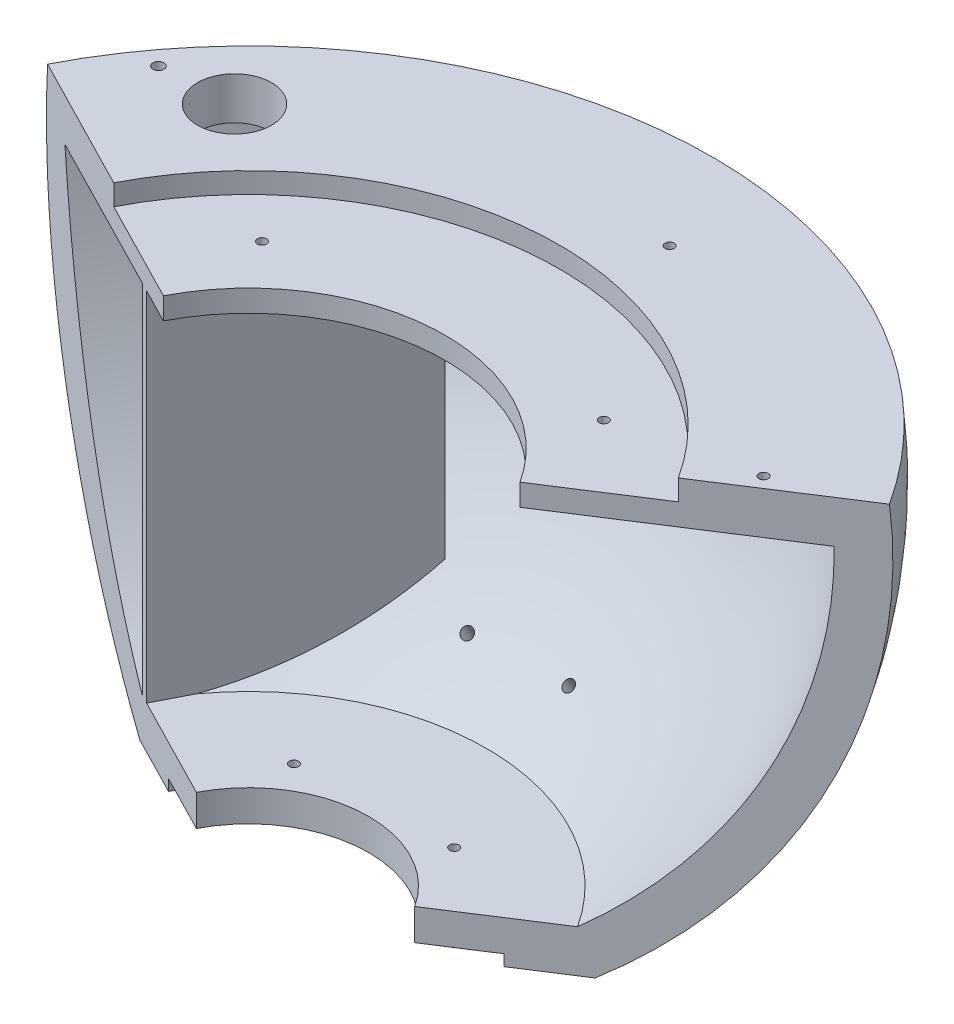
SolidWorks part; units mm, degrees
ref_plane "Plan de face" through (0, 0, 0) normal (0, 0, 1) x (1, 0, 0)
ref_plane "Plan de dessus" through (0, 0, 0) normal (0, 1, 0) x (1, 0, 0)
ref_plane "Plan de droite" through (0, 0, 0) normal (1, 0, 0) x (0, 0, -1)
sketch "Esquisse1" plane through (0, 0, 0) normal (0, 0, 1) x (1, 0, 0)
  line L0 (62.652, -45.2683) -> (117.5387, 212.9533) construction
  line L1 (0.3341, -92.6254) -> (0.3341, 171)
  line L2 (0, -110) -> (0, -296.0954) construction
  line L3 (0.3341, -92.6254) -> (59.3341, -92.6254)
  line L4 (0.3341, -92.6254) -> (0.3341, -77.5539) construction
  line L5 (0, 130.8616) -> (102, 130.8616) construction
  arc A0 (59.3341, -92.6254) -> (109.3586, 11.8616) centre (0, 0) ccw
  arc A1 (102, 130.8616) -> (83, 190.149) centre (0, 130.8616) ccw
  arc A3 (83, 190.149) -> (0.3341, 171) centre (15.1332, 295.1209) cw
  spline S0 degree 3 poles (102, 130.8616) (103.479, 113.6847) (71.2053, 65.5607) (110.7074, 34.2525) (109.3586, 11.8616) knots 0 0 0 0 0.406613 1 1 1 1
  dimension "D1" = 220
  dimension "D2" = 130.8616
  dimension "D3" = 102
  dimension "D8" = 12
  dimension "D9" = 110
  dimension "D12" = 59
  dimension "D13" = 281.0002
  dimension "D14" = 125
  dimension "D15" = 110
  dimension "D4" = 119
  dimension "D5" = 90
  dimension "D6" = 106
  dimension "D7" = 54
  dimension "D10" = 281
  dimension "D11" = 83
  dimension "D16" = 102
  dimension "D17" = 104.4869
revolve "Révolution2" add sketch "Esquisse1" angle 360 about L1
sketch "Esquisse2" plane through (0, 0, 0) normal (0, 1, 0) x (1, 0, 0)
  line L0 (0.3341, 0) -> (-105.6003, 54.3362) construction
  line L1 (0.3341, 0) -> (98.5184, 63.3863) construction
  line L2 (0.3341, 0) -> (6.0228, -114.443) construction
  dimension "D1" = 120
  dimension "D2" = 120
sketch "Esquisse3" plane through (0, 0, 0) normal (0, 1, 0) x (1, 0, 0)
  line L0 (0.3341, 0) -> (-105.6003, 54.3362) construction
  line L1 (0.3341, 0) -> (98.5184, 63.3863) construction
  line L2 (-97.2444, 50.0502) -> (0.3341, 0)
  line L3 (0.3341, 0) -> (92.4682, 59.4804)
  arc A0 (-97.2444, 50.0502) -> (92.4682, 59.4804) centre (0.3341, 0) ccw
  circle A1 centre (0.3341, 0) radius 109.6659 construction
extrude "Enlèv. mat.-Extru.1" cut sketch "Esquisse3" against normal mid plane 410
sketch "Esquisse4" plane through (0, 0, 0) normal (0, 0, 1) x (1, 0, 0)
  line L1 (107.6727, 198.3746) -> (-112, 198.3746)
  line L2 (107.6727, 198.3746) -> (107.6727, 11.3746)
  line L3 (107.6727, 11.3746) -> (-112, 11.3746)
  line L4 (-112, 198.3746) -> (-112, 11.3746)
  line L5 (-52.1629, -92.6254) -> (49.9021, -92.6254) construction
  dimension "D1" = 104
  dimension "D2" = 187
  dimension "D3" = 112
extrude "Enlèv. mat.-Extru.2" cut sketch "Esquisse4" against normal through all
shell "Coque2" thickness 10 removed face at (38.7311, -42.3994, -24.7885) removed face at (-40.3318, -42.3994, -20.8585)
ref_plane "Plan1" through (0, 11.5, 0) normal (0, 1, 0) x (1, 0, 0)
sketch "Esquisse6" plane through (0, 11.5, 0) normal (0, 1, 0) x (1, 0, 0)
  line L0 (0.3341, 0) -> (-105.6003, 54.3362) construction
  line L1 (0.3341, 0) -> (98.5184, 63.3863) construction
  line L2 (-64.7515, 33.3839) -> (0.3341, 0)
  line L3 (0.3341, 0) -> (61.7882, 39.6739)
  arc A0 (-64.7515, 33.3839) -> (61.7882, 39.6739) centre (0.3341, 0) cw
  dimension "D1" = 73.1479
extrude "Enlèv. mat.-Extru.4" cut sketch "Esquisse6" against normal blind 5
sketch "Esquisse7" plane through (0, 11.5, 0) normal (0, 1, 0) x (1, 0, 0)
  line L0 (0.3341, 0) -> (-105.6003, 54.3362) construction
  line L1 (0.3341, 0) -> (98.5184, 63.3863) construction
  line L2 (-40.7749, 21.0857) -> (0.3341, 0)
  line L3 (0.3341, 0) -> (39.1494, 25.0586)
  arc A0 (-40.7749, 21.0857) -> (39.1494, 25.0586) centre (0.3341, 0) cw
  dimension "D1" = 46.2013
extrude "Enlèv. mat.-Extru.5" cut sketch "Esquisse7" against normal blind 25
ref_plane "Plan2" through (0, -92.5, 0) normal (0, 1, 0) x (1, 0, 0)
sketch "Esquisse8" plane through (0, -92.5, 0) normal (0, 1, 0) x (1, 0, 0)
  line L0 (0.3341, 0) -> (98.5184, 63.3863) construction
  line L1 (0.3341, 0) -> (-105.6003, 54.3362) construction
  line L2 (36.8282, 23.56) -> (0.3341, 0)
  line L3 (0.3341, 0) -> (-38.3164, 19.8247)
  arc A0 (36.8282, 23.56) -> (-38.3164, 19.8247) centre (0.3341, 0) ccw
  dimension "D1" = 43.4383
extrude "Enlèv. mat.-Extru.6" cut sketch "Esquisse8" along normal mid plane 5
sketch "Esquisse10" plane through (0, -92.5, 0) normal (0, 1, 0) x (1, 0, 0)
  line L0 (0.3341, 0) -> (98.5184, 63.3863) construction
  line L1 (0.3341, 0) -> (-105.6003, 54.3362) construction
  line L2 (-24.8381, 12.9114) -> (0.3341, 0)
  line L3 (0.3341, 0) -> (24.1019, 15.3441)
  arc A0 (24.1019, 15.3441) -> (-24.8381, 12.9114) centre (0.3341, 0) ccw
  dimension "D1" = 28.2904
extrude "Enlèv. mat.-Extru.10" cut sketch "Esquisse10" along normal blind 15
scale "Echelle1" scale about centroid uniform scaling yes scale factor 1.15
sketch "Esquisse11" plane through (0, 17.974, 0) normal (0, 1, 0) x (1, 0, 0)
  arc A0 (106.2495, 57.3541) -> (-110.7469, 46.5678) centre (0.8651, -10.6805) ccw construction
  point P1 (-104.7658, 56.971)
  point P2 (-52.0649, 103.0429)
  dimension "D1" = 12
  dimension "D2" = 70
sketch3d "Esquisse3D1"
  line L1 (-52.0649, 17.974, -103.0429) -> (-104.7658, 17.974, -56.971)
  line L2 (-52.0649, 17.974, -103.0429) -> (-52.0649, 79.5177, -103.0429)
  line L3 (-52.0649, 79.5177, -103.0429) -> (-104.7658, 79.5177, -56.971)
  line L4 (-104.7658, 17.974, -56.971) -> (-104.7658, 79.5177, -56.971)
ref_plane "Plan4" through (-73.6133, 0, -84.2049) normal (-0.6582, 0, -0.7529) x (-0.7529, 0, 0.6582)
ref_plane "Plan5" through (-78.8787, 0, -90.2279) normal (-0.6582, 0, -0.7529) x (-0.7529, 0, 0.6582)
sketch "Esquisse21" plane through (-4.157, 0, 8.1046) normal (-0.4564, 0, 0.8898) x (0.8898, 0, 0.4564)
  line L0 (-58.7509, -90.126) -> (-26.8898, -90.126) construction
  line L1 (-57.9607, -90.126) -> (-108.9607, -90.126)
  line L2 (-57.9607, -90.126) -> (-57.9607, 6.474)
  line L3 (-57.9607, 6.474) -> (-108.9607, 6.474)
  line L4 (-108.9607, -90.126) -> (-108.9607, 6.474)
  line L5 (-47.4873, 6.474) -> (-108.9607, 6.474) construction
  arc A0 (-108.9607, 6.474) -> (-58.7509, -90.126) centre (6.0284, 4.8932) ccw construction
  dimension "D1" = 51
  dimension "D2" = 96.6
extrude "Boss.-Extru.2" add sketch "Esquisse21" against normal blind 60
sketch "Esquisse22" plane through (-4.157, 0, 8.1046) normal (-0.4564, 0, 0.8898) x (0.8898, 0, 0.4564)
  line L0 (-78.4759, 17.974) -> (-119.7934, 17.974) construction
  line L1 (-62.2058, -101.626) -> (-148.1886, -101.626)
  line L2 (6.0284, 27.594) -> (6.0284, -115.4103) construction
  line L3 (-119.7934, 17.974) -> (-148.1886, 17.974)
  line L4 (-148.1886, -101.626) -> (-148.1886, 17.974)
  arc A0 (-62.2058, -101.626) -> (-108.9607, -47.8302) centre (6.0284, 4.8932) cw
  arc A2 (-77.4797, -90.126) -> (-62.2058, -101.626) centre (6.0284, 4.8932) ccw construction
  arc A3 (-119.7934, 17.974) -> (-108.9607, -47.8302) centre (6.0284, 4.8932) ccw
  arc A4 (-119.7934, 17.974) -> (-108.9607, -47.8302) centre (6.0284, 4.8932) ccw construction
  point P6 (-108.9607, -47.8302)
revolve "Enlèvement de matière-Révolution1" cut sketch "Esquisse22" angle 360 about L2
sketch "Esquisse12" plane through (-78.8787, 0, -90.2279) normal (-0.6582, 0, -0.7529) x (-0.7529, 0, 0.6582)
  line L1 (-3.296, 1.2051) -> (9.704, 1.2051)
  line L2 (-3.296, 1.2051) -> (-3.296, -17.4949)
  line L3 (-3.296, -17.4949) -> (9.704, -17.4949)
  line L4 (9.704, 1.2051) -> (9.704, -17.4949)
  dimension "D1" = 13
  dimension "D2" = 18.7
  dimension "D3" = 3.296
  dimension "D4" = 1.2051
extrude "Enlèv. mat.-Extru.12" cut sketch "Esquisse12" against normal blind 50
sketch "Esquisse13" plane through (-78.8787, 0, -90.2279) normal (-0.6582, 0, -0.7529) x (-0.7529, 0, 0.6582)
  circle A0 centre (2.99, -80.5) radius 2.75
  dimension "D1" = 5.5
  dimension "D2" = 80.5
extrude "Enlèv. mat.-Extru.13" cut sketch "Esquisse13" against normal blind 50
sketch "Esquisse14" plane through (-78.8787, 0, -90.2279) normal (-0.6582, 0, -0.7529) x (-0.7529, 0, 0.6582)
  circle A0 centre (2.99, -80.5) radius 3.25
  dimension "D1" = 6.5
extrude "Enlèv. mat.-Extru.14" cut sketch "Esquisse14" against normal blind 42
sketch "Esquisse15" plane through (-78.8787, 0, -90.2279) normal (-0.6582, 0, -0.7529) x (-0.7529, 0, 0.6582)
  line L1 (-4.2483, 2.2976) -> (10.7517, 2.2976)
  line L2 (-4.2483, 2.2976) -> (-4.2483, -18.7024)
  line L3 (-4.2483, -18.7024) -> (10.7517, -18.7024)
  line L4 (10.7517, 2.2976) -> (10.7517, -18.7024)
  dimension "D1" = 15
  dimension "D2" = 21
  dimension "D3" = 2.2976
  dimension "D4" = 4.2483
extrude "Enlèv. mat.-Extru.15" cut sketch "Esquisse15" against normal blind 6.5
ref_plane "Plan7" through (0.4069, 0, -0.7932) normal (-0.4564, 0, 0.8898) x (0.8898, 0, 0.4564)
ref_plane "Plan8" through (-35.4394, 0, -40.5385) normal (-0.6582, 0, -0.7529) x (-0.7529, 0, 0.6582)
sketch "Esquisse23" plane through (-4.157, 0, 8.1046) normal (-0.4564, 0, 0.8898) x (0.8898, 0, 0.4564)
  line L0 (-60.5449, -74.5019) -> (-60.5449, -90.1574)
  line L1 (-108.9607, 6.474) -> (-60.5449, 6.474)
  line L4 (-60.5449, 6.474) -> (-60.5449, -74.5019)
  line L5 (-60.5449, -90.1574) -> (-60.6003, -90.1574)
  spline S0 degree 3 poles (-108.9607, 6.474) (-103.0847, -29.155) (-88.7059, -66.4238) (-60.6003, -90.1574) knots 0 0 0 0 1 1 1 1
extrude "Enlèv. mat.-Extru.16" cut sketch "Esquisse23" against normal blind 50
sketch "Esquisse24" plane through (0, 17.974, 0) normal (0, 1, 0) x (1, 0, 0)
  line L0 (-73.9834, 27.7109) -> (-110.7469, 46.5678) construction
  line L1 (106.2495, 57.3541) -> (71.5372, 34.9444) construction
  circle A0 centre (-76.1349, 62.5307) radius 10
  arc A1 (106.2495, 57.3541) -> (-110.7469, 46.5678) centre (0.8651, -10.6805) ccw construction
  circle A3 centre (0.5514, -4.3702) radius 101.767 construction
  point P10 (-92.3651, 37.1394)
  point P11 (88.8934, 46.1493)
  dimension "D1" = 20
  dimension "D2" = 30
  dimension "D3" = 77
  dimension "D4" = 62.5307
  dimension "D5" = 76.1349
extrude "Enlèv. mat.-Extru.17" cut sketch "Esquisse24" against normal blind 20
sketch "Esquisse25" plane through (0, -98.6068, 0) normal (0, -1, 0) x (1, 0, 0)
  line L0 (-1.615, -39.212) -> (0.3341, 0) construction
  line L1 (0.3341, 0) -> (6.0228, 114.443) construction
  line L2 (0.8656, 10.692) -> (19.7396, -26.1048) construction
  line L3 (-40.1239, -31.6247) -> (-47.9228, -31.6247) construction
  line L4 (0.8656, 10.692) -> (-21.5644, -24.0517) construction
  circle A0 centre (19.7396, -26.1048) radius 1.25
  circle A2 centre (-21.5644, -24.0517) radius 1.25
  circle A4 centre (-1.1875, -30.612) radius 1.25
  circle A5 centre (0.8656, 10.692) radius 41.355 construction
  arc A6 (-43.5831, -12.118) -> (42.8332, -16.4135) centre (0.8651, 10.6805) ccw construction
  point P1 (-1.615, -39.212)
  dimension "D1" = 8.6
  dimension "D5" = 2.5
  dimension "D3" = 2.5
  dimension "D6" = 30
  dimension "D2" = 82.71
  dimension "D4" = 30
hole_wizard "Trou taraudé M31" positions "Esquisse27" profile "Esquisse26" tap size "M3" standard "Iso"
sketch "Esquisse27" plane through (0, -98.6068, 0) normal (0, -1, 0) x (-1, 0, 0)
  point P0 (21.5644, 24.0517)
  point P5 (-19.7396, 26.1048)
sketch "Esquisse26" plane through (-21.5644, -98.6068, -24.0517) normal (1, 0, 0) x (0, 0, -1)
  line L0 (0, 0) -> (0, 13.2511)
  line L1 (0, 13.2511) -> (1.25, 12.5)
  line L2 (1.25, 12.5) -> (1.25, 0)
  line L5 (1.25, 0) -> (0, 0)
  line L10 (0, 13.2511) -> (-1.25, 12.5) construction
  line L11 (0, -6.35) -> (0, 107.95) construction
  dimension "Diamètre du trou pour taraudage" = 2.5
  dimension "Profondeur du trou pour taraudage" = 12.5
  dimension "Angle de pointe" = 118
cosmetic thread "Filetage de perçage1" parameters "D1"=8.4808, "D2"=3
cosmetic thread "Filetage de perçage3" parameters "D1"=8.4808, "D2"=3
sketch "Esquisse28" plane through (0, 12.3682, 0) normal (0, 1, 0) x (1, 0, 0)
  line L0 (-1.7727, 42.3855) -> (-3.3112, 73.3359) construction
  line L1 (-73.9834, 27.7109) -> (-46.4103, 13.5681) construction
  line L2 (45.5026, 18.1369) -> (71.5372, 34.9444) construction
  line L3 (-45.8023, 39.6351) -> (0.8651, -10.6805) construction
  line L4 (42.3125, 44.0151) -> (0.8651, -10.6805) construction
  circle A0 centre (0.8651, -10.6805) radius 68.6258 construction
  arc A1 (45.5026, 18.1369) -> (-46.4103, 13.5681) centre (0.8651, -10.6805) ccw construction
  circle A3 centre (-45.8023, 39.6351) radius 1.5
  circle A4 centre (-2.542, 57.8607) radius 1.5
  circle A5 centre (42.3125, 44.0151) radius 1.5
  arc A6 (71.5372, 34.9444) -> (-73.9834, 27.7109) centre (0.8651, -10.6805) ccw construction
  point P11 (-2.542, 57.8607)
  point P12 (-60.1968, 20.6395)
  point P13 (58.5199, 26.5406)
  dimension "D1" = 3
  dimension "D2" = 40
  dimension "D3" = 40
hole_wizard "Trou taraudé M32" positions "Esquisse3D2" profile "Esquisse29" tap size "M3" standard "Iso"
sketch3d "Esquisse3D2"
  point P0 (-45.8023, 12.3682, -39.6351)
  point P6 (42.3125, 12.3682, -44.0151)
sketch "Esquisse29" plane through (-45.8023, 12.3682, -39.6351) normal (1, 0, 0) x (0, 0, 1)
  line L0 (0, 0) -> (0, 13.2511)
  line L1 (0, 13.2511) -> (1.25, 12.5)
  line L2 (1.25, 12.5) -> (1.25, 0)
  line L5 (1.25, 0) -> (0, 0)
  line L10 (0, 13.2511) -> (-1.25, 12.5) construction
  line L11 (0, -6.35) -> (0, 107.95) construction
  dimension "Diamètre du trou pour taraudage" = 2.5
  dimension "Profondeur du trou pour taraudage" = 12.5
  dimension "Angle de pointe" = 118
sketch "Esquisse30" [suppressed] plane through (0, 17.974, 0) normal (0, 1, 0) x (1, 0, 0)
  line L0 (-5.3625, 114.6024) -> (-4.1198, 89.6024) construction
  line L1 (-61.759, 67.8063) -> (0.8656, -10.692) construction
  line L2 (0.8656, -10.692) -> (37.5348, 82.7917) construction
  line L3 (-1.615, 39.212) -> (0.3341, 0) construction
  line L4 (-14.1198, 88.6018) -> (0.8656, -10.692) construction
  circle A0 centre (0.8656, -10.692) radius 100.4183 construction
  circle A2 centre (-14.1198, 88.6018) radius 1.5
  circle A3 centre (-61.759, 67.8063) radius 1.5
  circle A4 centre (37.5348, 82.7917) radius 1.5
  arc A6 (106.2495, 57.3541) -> (-110.7469, 46.5678) centre (0.8651, -10.6805) ccw construction
  point P5 (21.7748, 194.3628)
  point P6 (21.7748, 169.3628)
  point P15 (15.5473, 194.239)
  dimension "D2" = 3
  dimension "D1" = 25
  dimension "D3" = 10
  dimension "D4" = 30
  dimension "D5" = 30
hole_wizard "Trou taraudé M33" [suppressed] positions "Esquisse3D3" profile "Esquisse31" tap size "M3" standard "Iso"
sketch3d "Esquisse3D3" [suppressed]
  point P0 (-61.759, 17.974, -67.8063)
  point P6 (37.5348, 17.974, -82.7917)
  point P10 (-14.1198, 17.974, -88.6018)
sketch "Esquisse31" plane through (-61.759, 17.974, -67.8063) normal (1, 0, 0) x (0, 0, 1)
  line L0 (0, 0) -> (0, 13.2511)
  line L1 (0, 13.2511) -> (1.25, 12.5)
  line L2 (1.25, 12.5) -> (1.25, 0)
  line L5 (1.25, 0) -> (0, 0)
  line L10 (0, 13.2511) -> (-1.25, 12.5) construction
  line L11 (0, -6.35) -> (0, 107.95) construction
  dimension "Diamètre du trou pour taraudage" = 2.5
  dimension "Profondeur du trou pour taraudage" = 12.5
  dimension "Angle de pointe" = 118
sketch "Esquisse32" plane through (0, 17.974, 0) normal (0, 1, 0) x (1, 0, 0)
  circle A0 centre (82.6176, 46.9087) radius 1.6936
  circle A1 centre (53.5071, 74.3419) radius 1.7579
  circle A2 centre (15.9739, 88.1715) radius 1.5897
hole_wizard "Trou taraudé M34" positions "Esquisse3D4" profile "Esquisse33" tap size "M3" standard "Iso"
sketch3d "Esquisse3D4"
  point P0 (15.9739, 17.974, -88.1715)
  point P6 (82.6176, 17.974, -46.9087)
sketch "Esquisse33" plane through (15.9739, 17.974, -88.1715) normal (1, 0, 0) x (0, 0, 1)
  line L0 (0, 0) -> (0, 13.2511)
  line L1 (0, 13.2511) -> (1.25, 12.5)
  line L2 (1.25, 12.5) -> (1.25, 0)
  line L5 (1.25, 0) -> (0, 0)
  line L10 (0, 13.2511) -> (-1.25, 12.5) construction
  line L11 (0, -6.35) -> (0, 107.95) construction
  dimension "Diamètre du trou pour taraudage" = 2.5
  dimension "Profondeur du trou pour taraudage" = 12.5
  dimension "Angle de pointe" = 118
ref_plane "Plan9" through (0, 7.974, 0) normal (0, 1, 0) x (1, 0, 0)
sketch "Esquisse34" plane through (0, 7.974, 0) normal (0, 1, 0) x (1, 0, 0)
  line L0 (-73.9834, 27.7109) -> (-110.7469, 46.5678) construction
  circle A0 centre (-95.3017, 61.1231) radius 1.5
  circle A1 centre (0.3341, 0) radius 113.5 construction
  dimension "D3" = 3
  dimension "D2" = 227
  dimension "D1" = 20
extrude "Enlèv. mat.-Extru.18" cut sketch "Esquisse34" against normal mid plane 100
sketch "Esquisse35" plane through (0, 7.974, 0) normal (0, 1, 0) x (1, 0, 0)
  circle A0 centre (-95.3017, 61.1231) radius 4.7
  dimension "D1" = 9.4
extrude "Enlèv. mat.-Extru.19" cut sketch "Esquisse35" against normal blind 100
sketch3d "Esquisse3D5"
  point P0 (8.4606, -94.2857, -76.8932)
  point P1 (-17.4955, -94.196, -75.3858)
  point P2 (7.7426, -94.7745, -75.9943)
  point P4 (9.3143, -93.8555, -77.6986)
  point P5 (7.3595, -93.9616, -77.3882)
  point P6 (-17.4871, -94.8178, -74.3014)
  point P7 (-16.3115, -94.0305, -75.7506)
  point P8 (-18.3294, -93.7101, -76.1802)
ref_plane "Plan10" through (-3.8135, -103.8088, -59.4884) normal (0.0319, 0.8672, 0.497) x (0.9995, -0.0276, -0.0158)
sketch "Esquisse36" plane through (-3.8135, -103.8088, -59.4884) normal (0.0319, 0.8672, 0.497) x (0.9995, -0.0276, -0.0158)
  circle A0 centre (12.2803, 19.8359) radius 1.5
  circle A1 centre (-13.689, 18.5726) radius 1.5
  dimension "D1" = 3
extrude "Enlèv. mat.-Extru.20" cut sketch "Esquisse36" along normal blind 40
